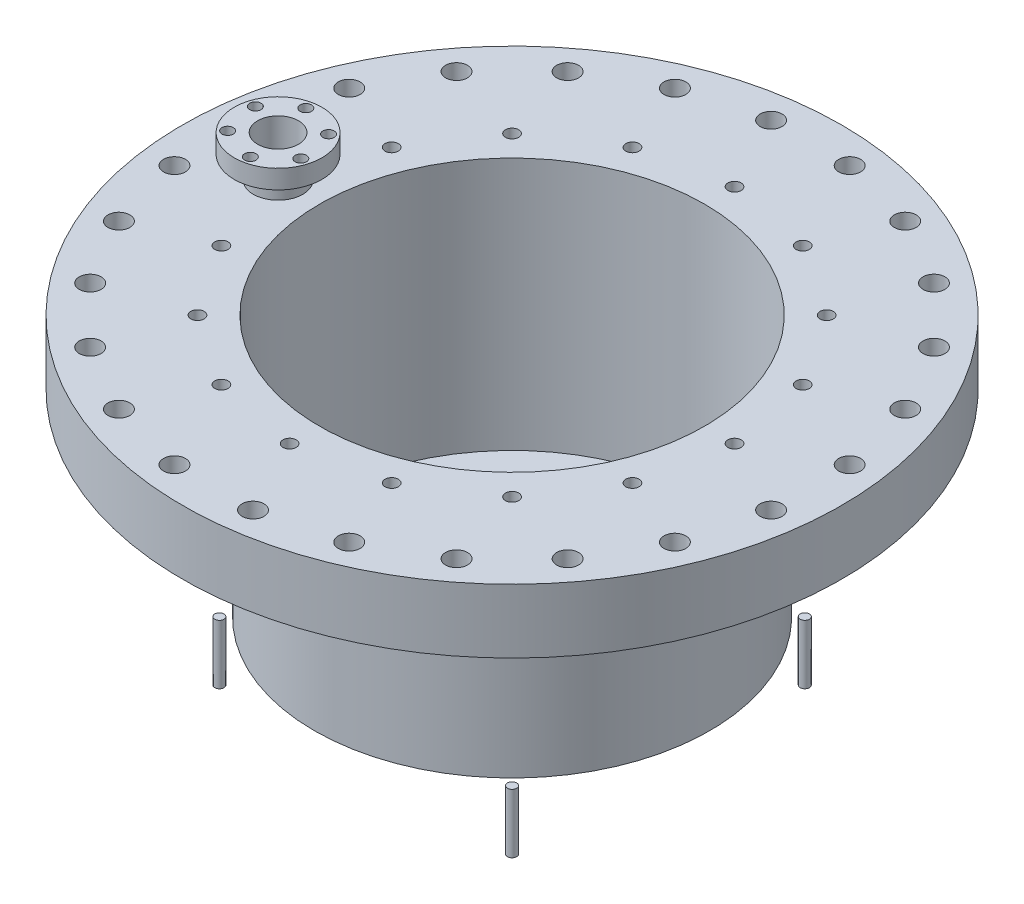
SolidWorks part; units mm, degrees
note: '?' marks a value the reader was unsure of.
ref_plane "Front Plane" through (0, 0, 0) normal (0, 0, 1) x (1, 0, 0)
ref_plane "Top Plane" through (0, 0, 0) normal (0, 1, 0) x (1, 0, 0)
ref_plane "Right Plane" through (0, 0, 0) normal (1, 0, 0) x (0, 0, -1)
sketch "Sketch1" plane through (0, 0, 0) normal (0, 1, 0) x (1, 0, 0)
  circle A0 centre (0, 0) radius 76.2
  dimension "D1" = 152.4
extrude "Extrude1" add sketch "Sketch1" against normal blind 75.946
sketch "Sketch2" plane through (0, 0, 0) normal (0, 1, 0) x (1, 0, 0)
  circle A0 centre (0, 0) radius 127
extrude "Extrude2" add sketch "Sketch2" along normal blind 24.638
sketch "Sketch3" plane through (0, 0, 0) normal (0, 1, 0) x (1, 0, 0)
  circle A0 centre (0, 0) radius 74.168
  dimension "D1" = 148.336
extrude "Cut-Extrude1" cut sketch "Sketch3" against normal blind 72.9488 and the other way through all
sketch "Sketch4" plane through (0, 0, 0) normal (0, 1, 0) x (1, 0, 0)
  circle A0 centre (0, 0) radius 48.8061
  dimension "D1" = 97.6122
extrude "Cut-Extrude2" cut sketch "Sketch4" against normal through all
sketch "Sketch5" plane through (0, 0, 0) normal (0, 1, 0) x (1, 0, 0)
  line L0 (0, 0) -> (0, 108.8403)
  circle A0 centre (-15.1346, 114.959) radius 4.2164
  dimension "D2" = 115.951
ref_axis "Axis1" through (0, 130.3933, 0) along (0, -1, 0)?
sketch "Sketch8" plane through (0, 24.638, 0) normal (0, 1, 0) x (1, 0, 0)
  point P0 (0, 85.725)
hole_wizard "1/4-20 Tapped Hole1" positions "3DSketch1" profile "Sketch11" tap size "1/4-20" standard "Ansi Inch"
sketch3d "3DSketch1"
  point P0 (0, 24.638, -85.725)
sketch "Sketch11" plane through (0, 24.638, -85.725) normal (1, 0, 0) x (0, 0, 1)
  line L0 (0, 0) -> (0, 18.0438)
  line L1 (0, 18.0438) -> (2.5527, 16.51)
  line L2 (2.5527, 16.51) -> (2.5527, 0)
  line L5 (2.5527, 0) -> (0, 0)
  line L10 (0, 18.0438) -> (-2.5527, 16.51) construction
  line L11 (0, -6.35) -> (0, 107.95) construction
  dimension "Tap Drill Dia." = 5.1054
  dimension "Tap Drill Depth" = 16.51
  dimension "Drill Angle" = 118
cosmetic thread "Hole Thread1" parameters "D1"=12.7, "D2"=6.35
pattern_circular "CirPattern2" count 16 over 360 about axis through (0, 0, 0) along (0, 1, 0) skipping 4 of "1/4-20 Tapped Hole1"
ref_plane "Plane1" through (0, -75.946, 0) normal (0, -1, 0) x (1, 0, 0)
sketch "Sketch12" plane through (0, -75.946, 0) normal (0, -1, 0) x (1, 0, 0)
  point P0 (0, 0)
sketch "Sketch13" plane through (0, 0, 0) normal (1, 0, 0) x (0, 0, -1)
  line L0 (0, 0) -> (0, -106.8397)
ref_plane "Plane2" through (0, 24.638, 0) normal (0, 1, 0) x (-1, 0, 0)
sketch "Sketch14" plane through (0, 24.638, 0) normal (0, 1, 0) x (-1, 0, 0)
  line L0 (32.8055, 79.1996) -> (-48.6008, -117.3327)
  line L1 (-48.6008, -117.3327) -> (48.6008, 117.3327)
  circle A0 centre (0, 0) radius 127 construction
extrude "Cut-Extrude5" cut sketch "Sketch5" along normal through all contours A0
pattern_circular "CirPattern3" count 24 over 360 about axis through (0, 0, 0) along (0, 1, 0) of "Cut-Extrude5"
sketch "Sketch16" plane through (0, 24.638, 0) normal (0, 1, 0) x (-1, 0, 0)
  circle A0 centre (90.17, 0) radius 9.525
  dimension "D1" = 19.05
  dimension "D2" = 90.17
extrude "Extrude3" add sketch "Sketch16" along normal blind 8.636
ref_plane "Plane3" through (0, 33.274, 0) normal (0, 1, 0) x (-1, 0, 0)
sketch "Sketch17" plane through (0, 33.274, 0) normal (0, 1, 0) x (-1, 0, 0)
  circle A0 centre (90.17, 0) radius 16.891
  dimension "D1" = 33.782
extrude "Extrude5" add sketch "Sketch17" along normal blind 7.239
sketch "Sketch21" plane through (0, 33.274, 0) normal (0, 1, 0) x (-1, 0, 0)
  circle A0 centre (90.17, 0) radius 7.874
  dimension "D1" = 15.748
  dimension "D2" = 90.17
extrude "Cut-Extrude6" cut sketch "Sketch21" along normal through all and the other way through all
ref_plane "Plane4" through (0, 40.513, 0) normal (0, 1, 0) x (-1, 0, 0)
sketch "Sketch22" plane through (0, 40.513, 0) normal (0, 1, 0) x (-1, 0, 0)
  circle A0 centre (87.376, 13.4874) radius 2.1844
  dimension "D1" = 4.3688
extrude "Cut-Extrude7" cut sketch "Sketch22" against normal blind 7.239
ref_axis "Axis2" through (-90.17, 40.513, 0) along (0, -1, 0)?
pattern_circular "CirPattern4" count 6 over 360 about axis through (-90.17, 0, 0) along (0, 1, 0) of "Cut-Extrude7"
sketch "Sketch23" plane through (0, 40.513, 0) normal (0, 1, 0) x (-1, 0, 0)
  point P0 (90.17, 0)
sketch "Sketch24" plane through (0, 33.274, 0) normal (0, 1, 0) x (-1, 0, 0)
  point P0 (0, 0)
ref_plane "Plane5" through (0, -72.9488, 0) normal (0, 1, 0) x (-1, 0, 0)
sketch "Sketch25" plane through (0, -72.9488, 0) normal (0, 1, 0) x (-1, 0, 0)
  circle A0 centre (0, 0) radius 48.8061
  dimension "D1" = 97.6122
extrude "Extrude-Thin1" add sketch "Sketch25" along normal blind 10.0076 thin
sketch "Sketch28" plane through (0, 0, 0) normal (0, 1, 0) x (1, 0, 0)
  line L0 (0, 0) -> (-53.8815, -53.8815)
  line L1 (0, 0) -> (-91.1542, 0)
  circle A1 centre (-53.8815, -53.8815) radius 5.0894
  dimension "D1" = 45
ref_plane "Plane6" through (0, -75.946, 0) normal (0, -1, 0) x (1, 0, 0)
sketch "Sketch29" plane through (0, -75.946, 0) normal (0, -1, 0) x (1, 0, 0)
  line L0 (0, 0) -> (-56.396, 56.396)
  line L1 (0, 0) -> (-90.17, 0)
  line L2 (0, 0) -> (56.396, -56.396)
  line L3 (0, 0) -> (-56.396, -56.396)
  line L4 (0, 0) -> (56.396, 56.396)
  circle A1 centre (-56.396, 56.396) radius 1.778
  circle A2 centre (-56.396, -56.396) radius 1.778
  circle A3 centre (56.396, -56.396) radius 1.778
  circle A4 centre (56.396, 56.396) radius 1.778
  dimension "D1" = 3.556
  dimension "D6" = 3.556
  dimension "D7" = 3.556
  dimension "D8" = 3.556
  dimension "D2" = 79.756
  dimension "D3" = 79.756
  dimension "D4" = 79.756
  dimension "D5" = 79.756
extrude "Extrude7" add sketch "Sketch29" along normal blind 22.86 contours A2 | A1 | A4 | A3
ref_axis "Axis3" through (0, -62.9412, 0) along (0, -1, 0)?
ref_plane "Plane7" through (0, -98.806, 0) normal (0, -1, 0) x (1, 0, 0)
ref_plane "Plane8" through (0, 24.638, 0) normal (0, 1, 0) x (-1, 0, 0)
sketch "Sketch30" plane through (0, 24.638, 0) normal (0, 1, 0) x (-1, 0, 0)
  line L0 (0, 0) -> (90.17, 0)
